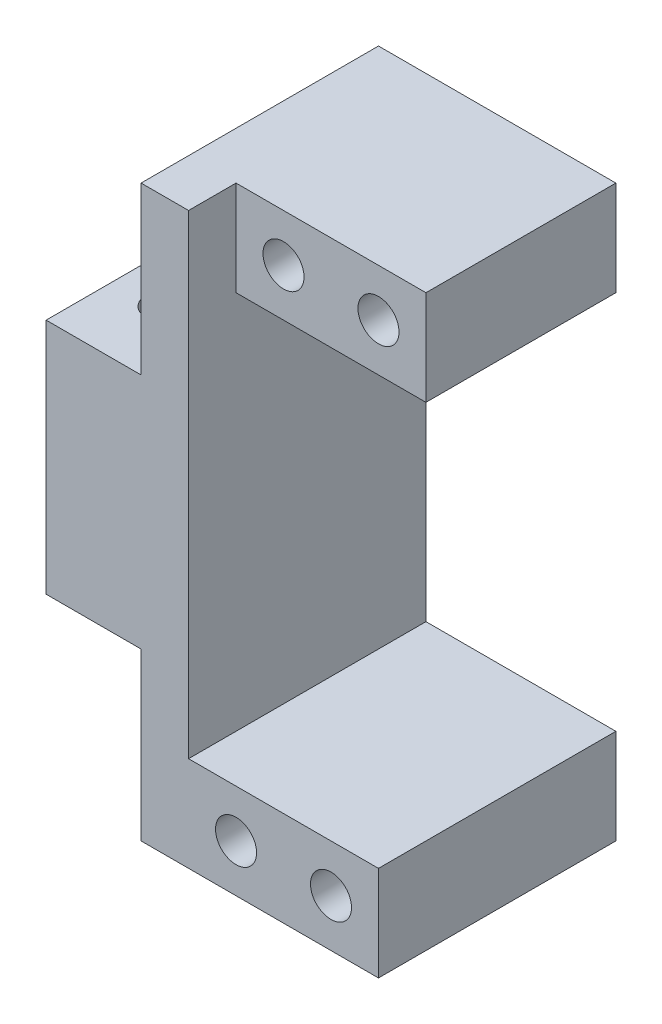
SolidWorks part; units mm, degrees
ref_plane "Plan de face" through (0, 0, 0) normal (0, 0, 1) x (1, 0, 0)
ref_plane "Plan de dessus" through (0, 0, 0) normal (0, 1, 0) x (1, 0, 0)
ref_plane "Plan de droite" through (0, 0, 0) normal (1, 0, 0) x (0, 0, -1)
sketch "Esquisse1" plane through (0, 0, 0) normal (0, 0, 1) x (1, 0, 0)
  line L0 (0, -12.5) -> (0, 12.5)
  line L1 (0, 12.5) -> (10, 12.5)
  line L2 (10, 12.5) -> (10, 30)
  line L3 (10, 30) -> (35, 30)
  line L4 (35, 30) -> (35, 20)
  line L5 (35, 20) -> (15, 20)
  line L6 (15, 20) -> (15, -20)
  line L7 (-90.4706, 0) -> (183.1231, 0) construction
  line L8 (35, -20) -> (15, -20)
  line L9 (35, -30) -> (35, -20)
  line L10 (10, -30) -> (35, -30)
  line L11 (10, -12.5) -> (10, -30)
  line L12 (0, -12.5) -> (10, -12.5)
  point P12 (15, 0)
  point P17 (0, 0)
  dimension "D1" = 10
  dimension "D2" = 20
  dimension "D3" = 5
  dimension "D4" = 40
  dimension "D5" = 10
  dimension "D6" = 25
extrude "Extrusion1" add sketch "Esquisse1" along normal blind 25
sketch "Esquisse2" plane through (0, 12.5, 0) normal (0, 1, 0) x (1, 0, 0)
  line L0 (-8.0322, -12.5) -> (41.2056, -12.5) construction
  line L2 (10, 0) -> (0, 0) construction
  line L3 (10, -25) -> (0, -25) construction
  line L4 (0, -25) -> (0, 0) construction
  circle A0 centre (5, -7.5) radius 2
  circle A1 centre (5, -17.5) radius 2
  dimension "D3" = 4
  dimension "D1" = 5
  dimension "D2" = 10
extrude "Enlèv. mat.-Extru.1" cut sketch "Esquisse2" against normal through all
sketch "Esquisse3" plane through (0, 0, 25) normal (0, 0, 1) x (1, 0, 0)
  line L0 (-17.3161, 0) -> (63.4117, 0) construction
  line L1 (10, -30) -> (35, -30) construction
  line L2 (35, 30) -> (10, 30) construction
  line L3 (25, 41.8458) -> (25, -35.7338) construction
  line L5 (15, -20) -> (15, 20) construction
  line L6 (35, 20) -> (35, 30) construction
  line L7 (15, 20) -> (35, 20) construction
  circle A0 centre (30, 25) radius 2.1614
  circle A1 centre (20, 25) radius 2.1614
  circle A2 centre (20, -25) radius 2.1614
  circle A3 centre (30, -25) radius 2.1614
  dimension "D1" = 5
  dimension "D2" = 10
extrude "Enlèv. mat.-Extru.2" cut sketch "Esquisse3" against normal through all
sketch "Esquisse4" plane through (0, 0, 25) normal (0, 0, 1) x (1, 0, 0)
  line L1 (35, 20) -> (15, 20)
  line L2 (35, 20) -> (35, 30)
  line L3 (35, 30) -> (15, 30)
  line L4 (15, 20) -> (15, 30)
extrude "Enlèv. mat.-Extru.3" cut sketch "Esquisse4" against normal blind 5
